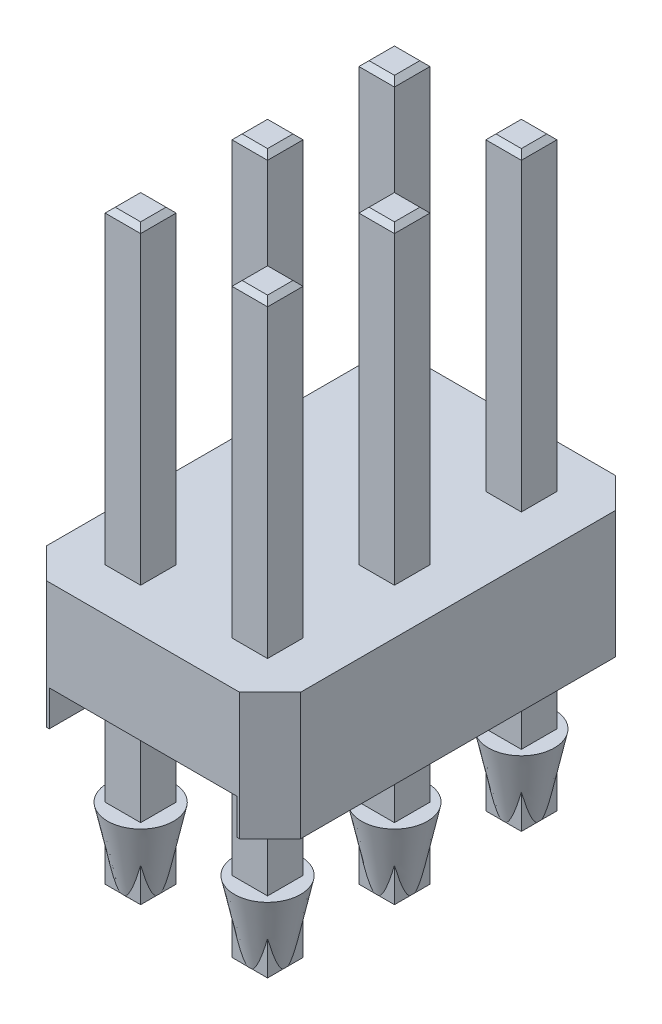
SolidWorks part; units mm, degrees
ref_plane "Plan de face" through (0, 0, 0) normal (0, 0, 1) x (1, 0, 0)
ref_plane "Plan de dessus" through (0, 0, 0) normal (0, 1, 0) x (1, 0, 0)
ref_plane "Plan de droite" through (0, 0, 0) normal (1, 0, 0) x (0, 0, -1)
sketch "Esquisse1" plane through (0, 0, 0) normal (0, 1, 0) x (1, 0, 0)
  line L1 (0, 0) -> (5, 0)
  line L2 (0, 0) -> (0, 7.4)
  line L3 (0, 7.4) -> (5, 7.4)
  line L4 (5, 0) -> (5, 7.4)
  dimension "D1" = 7.4
  dimension "D2" = 5
extrude "Boss.-Extru.1" add sketch "Esquisse1" along normal blind 2.5
sketch "Esquisse3" plane through (0, 0, 0) normal (0, 0, 1) x (1, 0, 0)
  line L0 (0, 0) -> (5, 0) construction
  line L1 (0.65, 0) -> (4.35, 0)
  line L2 (0.65, 0) -> (0.65, 0.7)
  line L3 (0.65, 0.7) -> (4.35, 0.7)
  line L4 (4.35, 0) -> (4.35, 0.7)
  line L5 (2.5, 2.5) -> (2.5, 0) construction
  line L6 (0, 2.5) -> (5, 2.5) construction
  point P6 (2.5, 0.7)
  dimension "D1" = 0.7
  dimension "D2" = 3.7
extrude "Enlèv. mat.-Extru.1" cut sketch "Esquisse3" against normal through all
sketch "Esquisse2" plane through (0, 2.5, 0) normal (0, 1, 0) x (1, 0, 0)
  line L0 (2.5, 7.4) -> (2.5, 0) construction
  line L1 (5, 7.4) -> (0, 7.4) construction
  line L2 (0, 0) -> (5, 0) construction
  line L3 (1.25, 6.55) -> (1.25, 0.5742) construction
  line L4 (0.9, 6.55) -> (1.6, 6.55)
  line L5 (0.9, 6.55) -> (0.9, 5.85)
  line L6 (0.9, 5.85) -> (1.6, 5.85)
  line L7 (1.6, 6.55) -> (1.6, 5.85)
  line L8 (0.9, 4.05) -> (1.6, 4.05)
  line L9 (0.9, 4.05) -> (0.9, 3.35)
  line L10 (0.9, 3.35) -> (1.6, 3.35)
  line L11 (1.6, 4.05) -> (1.6, 3.35)
  line L12 (0.9, 1.55) -> (1.6, 1.55)
  line L13 (0.9, 1.55) -> (0.9, 0.85)
  line L14 (0.9, 0.85) -> (1.6, 0.85)
  line L15 (1.6, 1.55) -> (1.6, 0.85)
  line L16 (0.9, 1.55) -> (0.9, 0.85)
  line L17 (1.6, 1.55) -> (1.6, 0.85)
  line L18 (0.9, 4.05) -> (0.9, 3.35)
  line L19 (1.6, 4.05) -> (1.6, 3.35)
  line L20 (0.9, 6.55) -> (0.9, 5.85)
  line L21 (1.6, 6.55) -> (1.6, 5.85)
  line L22 (0.9, 6.55) -> (0.9, 5.85)
  line L23 (1.6, 6.55) -> (1.6, 5.85)
  line L24 (0.9, 4.05) -> (0.9, 3.35)
  line L25 (1.6, 4.05) -> (1.6, 3.35)
  line L26 (0.9, 1.55) -> (0.9, 0.85)
  line L27 (1.6, 1.55) -> (1.6, 0.85)
  line L28 (0.9, 1.55) -> (0.9, 0.85)
  line L29 (1.6, 1.55) -> (1.6, 0.85)
  line L30 (0.9, 4.05) -> (0.9, 3.35)
  line L31 (1.6, 4.05) -> (1.6, 3.35)
  line L32 (0.9, 6.55) -> (0.9, 5.85)
  line L33 (1.6, 6.55) -> (1.6, 5.85)
  line L34 (3.4, 6.55) -> (3.4, 5.85)
  line L35 (4.1, 6.55) -> (4.1, 5.85)
  line L36 (3.4, 4.05) -> (3.4, 3.35)
  line L37 (4.1, 4.05) -> (4.1, 3.35)
  line L38 (3.4, 1.55) -> (3.4, 0.85)
  line L39 (4.1, 1.55) -> (4.1, 0.85)
  line L40 (3.4, 1.55) -> (3.4, 0.85)
  line L41 (4.1, 1.55) -> (4.1, 0.85)
  line L42 (3.4, 4.05) -> (3.4, 3.35)
  line L43 (4.1, 4.05) -> (4.1, 3.35)
  line L44 (3.4, 6.55) -> (3.4, 5.85)
  line L45 (4.1, 6.55) -> (4.1, 5.85)
  line L46 (3.4, 6.55) -> (3.4, 5.85)
  line L47 (4.1, 6.55) -> (4.1, 5.85)
  line L48 (3.4, 4.05) -> (3.4, 3.35)
  line L49 (4.1, 4.05) -> (4.1, 3.35)
  line L50 (3.4, 1.55) -> (3.4, 0.85)
  line L51 (4.1, 1.55) -> (4.1, 0.85)
  line L52 (3.4, 1.55) -> (3.4, 0.85)
  line L53 (4.1, 0.85) -> (3.4, 0.85)
  line L54 (4.1, 1.55) -> (4.1, 0.85)
  line L55 (4.1, 1.55) -> (3.4, 1.55)
  line L56 (3.4, 4.05) -> (3.4, 3.35)
  line L57 (4.1, 3.35) -> (3.4, 3.35)
  line L58 (4.1, 4.05) -> (4.1, 3.35)
  line L59 (4.1, 4.05) -> (3.4, 4.05)
  line L60 (3.4, 6.55) -> (3.4, 5.85)
  line L61 (4.1, 5.85) -> (3.4, 5.85)
  line L62 (4.1, 6.55) -> (4.1, 5.85)
  line L63 (4.1, 6.55) -> (3.4, 6.55)
  point P20 (1.25, 1.55)
  point P21 (1.25, 4.05)
  point P34 (3.75, 4.05)
  point P35 (3.75, 1.55)
  dimension "D1" = 0.85
  dimension "D2" = 1.8
  dimension "D3" = 1.8
  dimension "D4" = 0.9
  dimension "D5" = 0.7
extrude "Boss.-Extru.2" add sketch "Esquisse2" along normal blind 6.1 and the other way blind 5.5 contours L7 L4 L5 L6 | L35 L63 L34 L61 | L11 L8 L9 L10 | L37 L59 L36 L57 | L15 L12 L13 L14 | L39 L55 L38 L53 region at (1.25, 2.5, -6.2) region at (1.25, 2.5, -3.7) region at (1.25, 2.5, -1.2) region at (3.75, 2.5, -6.2) region at (3.75, 2.5, -3.7) region at (3.75, 2.5, -1.2)
ref_plane "Plan1" through (0, -1.55, 0) normal (0, 1, 0) x (1, 0, 0)
sketch "Esquisse4" plane through (0, -1.55, 0) normal (0, 1, 0) x (1, 0, 0)
  line L0 (2.5, 0) -> (2.5, 7.4) construction
  line L1 (4.35, 0) -> (0.65, 0) construction
  line L2 (4.35, 7.4) -> (0.65, 7.4) construction
  line L3 (1.25, 0.85) -> (1.25, 6.55) construction
  line L4 (0.9, 0.85) -> (1.6, 0.85) construction
  line L5 (0.9, 6.55) -> (1.6, 6.55) construction
  line L6 (0.9, 1.2) -> (1.6, 1.2) construction
  line L7 (0.9, 1.55) -> (0.9, 0.85) construction
  line L8 (1.6, 1.55) -> (1.6, 0.85) construction
  line L9 (0.9, 3.7) -> (1.6, 3.7) construction
  line L10 (0.9, 4.05) -> (0.9, 3.35) construction
  line L11 (1.6, 4.05) -> (1.6, 3.35) construction
  line L12 (0.9, 6.2) -> (1.6, 6.2) construction
  line L13 (0.9, 6.55) -> (0.9, 5.85) construction
  line L14 (1.6, 6.55) -> (1.6, 5.85) construction
  circle A0 centre (1.25, 6.2) radius 0.65
  circle A1 centre (1.25, 3.7) radius 0.65
  circle A2 centre (1.25, 1.2) radius 0.65
  circle A3 centre (3.75, 6.2) radius 0.65
  circle A4 centre (3.75, 3.7) radius 0.65
  circle A5 centre (3.75, 1.2) radius 0.65
  dimension "D1" = 1.3
extrude "Boss.-Extru.3" add sketch "Esquisse4" against normal blind 1.4 draft 12
chamfer "Chanfrein1" distance 0.1 angle 45 24 edges at (3.75, 8.6, -3.35) (3.4, 8.6, -3.7) (3.75, 8.6, -4.05) (4.1, 8.6, -3.7) (3.75, 8.6, -5.85) (3.4, 8.6, -6.2) (3.75, 8.6, -6.55) (4.1, 8.6, -6.2) (1.25, 8.6, -5.85) (0.9, 8.6, -6.2) (1.25, 8.6, -6.55) (1.6, 8.6, -6.2) (1.25, 8.6, -3.35) (0.9, 8.6, -3.7) (1.25, 8.6, -4.05) (1.6, 8.6, -3.7) (1.25, 8.6, -0.85) (0.9, 8.6, -1.2) (1.25, 8.6, -1.55) (1.6, 8.6, -1.2) (3.75, 8.6, -0.85) (3.4, 8.6, -1.2) (3.75, 8.6, -1.55) (4.1, 8.6, -1.2)
chamfer "Chanfrein2" distance 0.6 angle 45 4 edges at (0, 1.25, -7.4) (5, 1.25, -7.4) (0, 1.25, 0) (5, 1.25, 0)
chamfer "Chanfrein3" distance 0.05 angle 45 24 edges at (1.25, -3, -6.55) (0.9, -3, -6.2) (1.25, -3, -5.85) (1.6, -3, -6.2) (3.75, -3, -6.55) (3.4, -3, -6.2) (3.75, -3, -5.85) (4.1, -3, -6.2) (1.25, -3, -4.05) (0.9, -3, -3.7) (1.25, -3, -3.35) (1.6, -3, -3.7) (3.75, -3, -4.05) (3.4, -3, -3.7) (3.75, -3, -3.35) (4.1, -3, -3.7) (3.75, -3, -1.55) (3.4, -3, -1.2) (3.75, -3, -0.85) (4.1, -3, -1.2) (1.25, -3, -1.55) (0.9, -3, -1.2) (1.25, -3, -0.85) (1.6, -3, -1.2)
